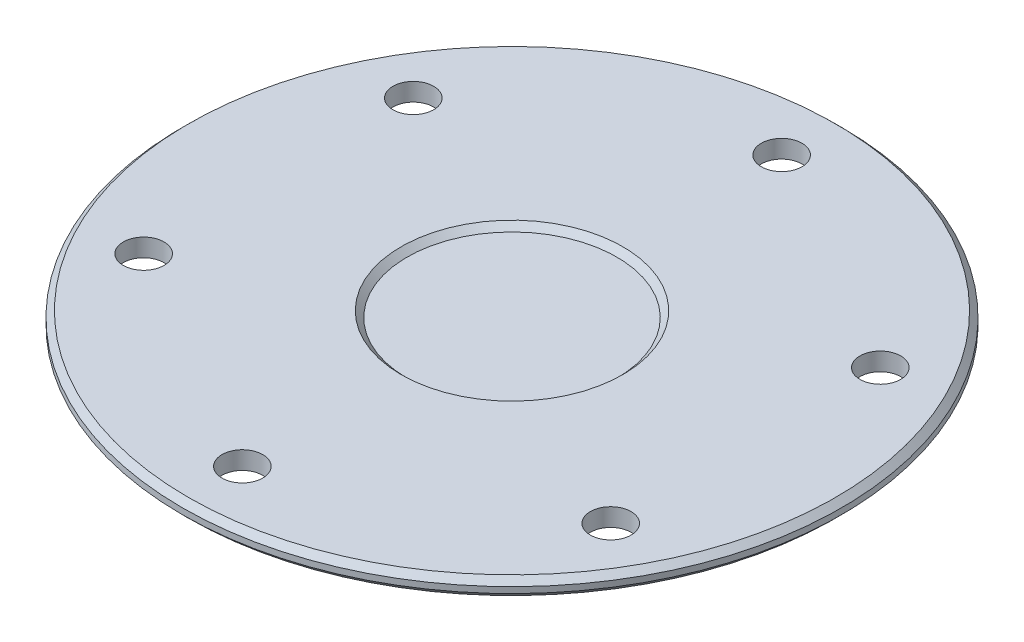
SolidWorks part; units mm, degrees
ref_plane "前视基准面" through (0, 0, 0) normal (0, 0, 1) x (1, 0, 0)
ref_plane "上视基准面" through (0, 0, 0) normal (0, 1, 0) x (1, 0, 0)
ref_plane "右视基准面" through (0, 0, 0) normal (1, 0, 0) x (0, 0, -1)
sketch "草图1" plane through (0, 0, 0) normal (0, 1, 0) x (1, 0, 0)
  circle A0 centre (0, 0) radius 55
  dimension "D1" = 110
extrude "凸台-拉伸1" add sketch "草图1" along normal blind 3
sketch "草图2" plane through (0, 3, 0) normal (0, 1, 0) x (1, 0, 0)
  line L0 (0, 0) -> (0, 59.7232)
  circle A0 centre (0, 0) radius 45
  dimension "D1" = 90
hole_wizard "M8 螺纹孔的螺纹孔钻头1" positions "草图3" profile "草图4" hole size "M8" standard "GB"
sketch "草图3" plane through (0, 3, 0) normal (0, 1, 0) x (1, 0, 0)
  line L0 (0, 0) -> (0, 59.7232) construction
  circle A0 centre (0, 0) radius 45 construction
  point P0 (0, 45)
sketch "草图4" plane through (0, 3, -45) normal (1, 0, 0) x (0, 0, 1)
  line L0 (0, 0) -> (0, 18.0429)
  line L1 (0, 18.0429) -> (3.4, 16)
  line L2 (3.4, 16) -> (3.4, 0)
  line L5 (3.4, 0) -> (0, 0)
  line L10 (0, 18.0429) -> (-3.4, 16) construction
  line L11 (0, -6.35) -> (0, 107.95) construction
  dimension "孔直径" = 6.8
  dimension "孔深度" = 16
  dimension "导头角度" = 118
pattern_circular "阵列(圆周)1" count 6 over 360 about axis through (0, 3, 0) along (0, -1, 0) of "M8 螺纹孔的螺纹孔钻头1" reverse direction yes
sketch "草图5" plane through (0, 3, 0) normal (0, 1, 0) x (1, 0, 0)
  circle A0 centre (0, 0) radius 17.5
  dimension "D1" = 35
extrude "切除-拉伸1" cut sketch "草图5" against normal blind 1
chamfer "倒角1" distance 1 angle 45 3 edges at (0, 3, 17.5) (0, 0, 55) (0, 3, 55)
